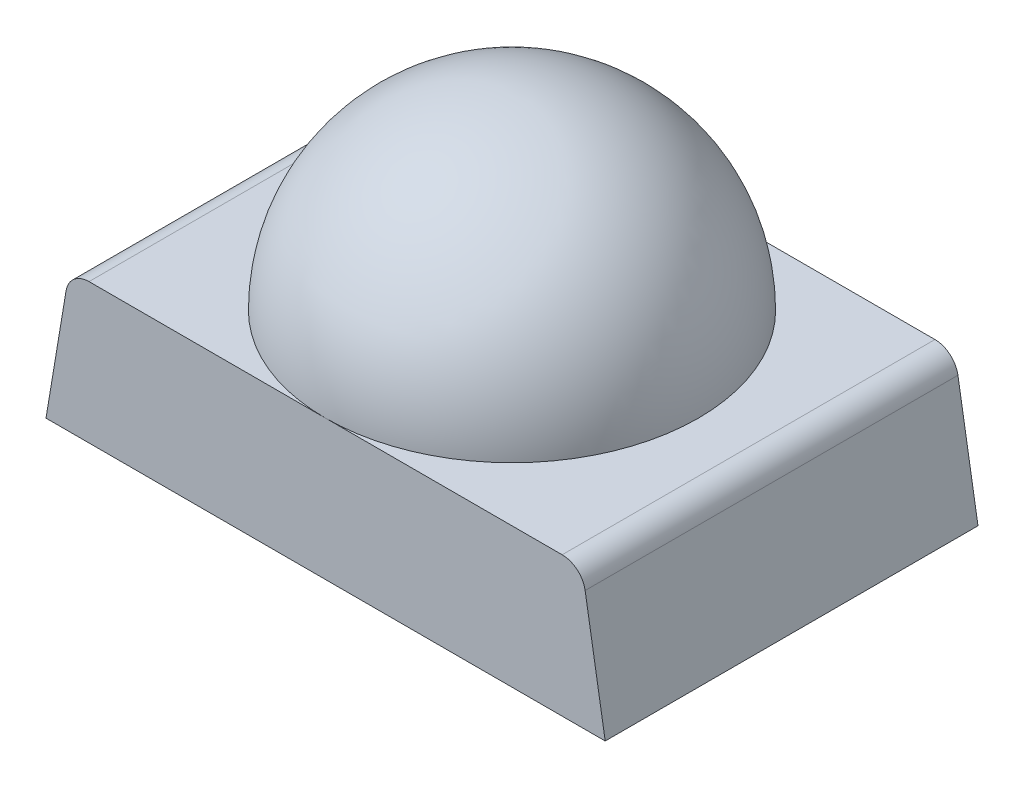
SolidWorks part; units mm, degrees
ref_plane "Front Plane" through (0, 0, 0) normal (0, 0, 1) x (1, 0, 0)
ref_plane "Top Plane" through (0, 0, 0) normal (0, 1, 0) x (1, 0, 0)
ref_plane "Right Plane" through (0, 0, 0) normal (1, 0, 0) x (0, 0, -1)
ref_axis "Axis1" through (0, 0.02, 0) along (0, 1, 0)
sketch "Sketch1" plane through (0, 0, 0) normal (0, 1, 0) x (1, 0, 0)
  line L1 (-0.6, -0.4) -> (0.6, -0.4)
  line L2 (-0.6, -0.4) -> (-0.6, 0.4)
  line L3 (-0.6, 0.4) -> (0.6, 0.4)
  line L4 (0.6, -0.4) -> (0.6, 0.4)
  line L5 (-0.6, -0.4) -> (0.6, 0.4) construction
  line L6 (-0.6, 0.4) -> (0.6, -0.4) construction
  point P0 (0, 0)
  dimension "D1" = 1.2
  dimension "D2" = 0.8
extrude "Boss-Extrude1" add sketch "Sketch1" along normal blind 0.3
sketch "Sketch5" plane through (0, 0, 0) normal (1, 0, 0) x (0, 0, -1)
  line L0 (0, 0) -> (0, 0.7)
  line L1 (0.4, 0) -> (-0.4, 0) construction
  line L2 (0.4, 0) -> (0, 0)
  line L3 (0.4, 0.3) -> (0.4, 0) construction
  line L4 (0.4, 0.3) -> (0.4, 0)
  arc A0 (0, 0.7) -> (0.4, 0.3) centre (0, 0.3) cw
  dimension "D1" = 0.7
revolve "Revolve1" add sketch "Sketch5" angle 360 about L0
sketch "Sketch4" plane through (0, 0, 0.4) normal (0, 0, 1) x (1, 0, 0)
  line L0 (-0.6, 0) -> (-0.55, 0.3)
  line L1 (-0.6, 0.3) -> (0, 0.3) construction
  line L2 (-0.55, 0.3) -> (-0.6, 0.3)
  line L3 (-0.6, 0.3) -> (-0.6, 0)
  dimension "D1" = 0.05
extrude "Cut-Extrude1" cut sketch "Sketch4" against normal through all
mirror "Mirror1" about plane through (0, 0, 0) normal (1, 0, 0) of "Cut-Extrude1"
fillet "Fillet1" radius 0.05 2 edges at (0.55, 0.3, 0) (-0.55, 0.3, 0)
